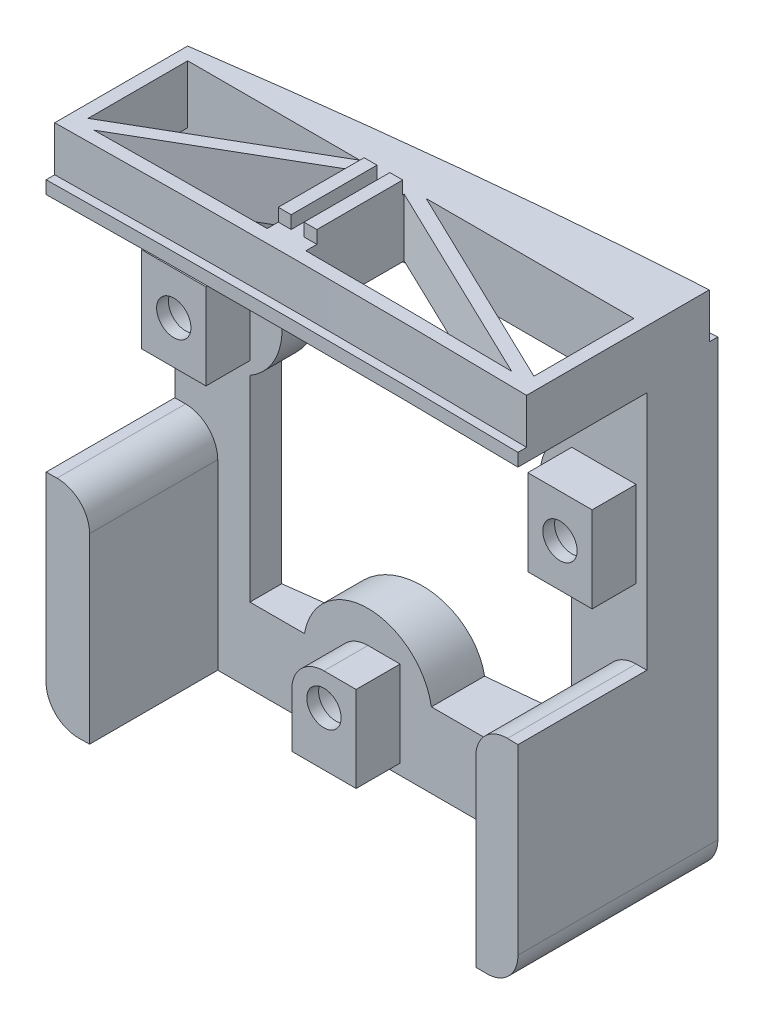
SolidWorks part; units mm, degrees
ref_plane "Front Plane" through (0, 0, 0) normal (0, 0, 1) x (1, 0, 0)
ref_plane "Top Plane" through (0, 0, 0) normal (0, 1, 0) x (1, 0, 0)
ref_plane "Right Plane" through (0, 0, 0) normal (1, 0, 0) x (0, 0, -1)
sketch "Sketch1" plane through (0, 0, 0) normal (0, 1, 0) x (1, 0, 0)
  line L0 (-144.1303, -12.9929) -> (155.8697, -12.8308) construction
  line L1 (-29.3738, 9.8314) -> (-29.3738, -4.1686)
  line L2 (14.6262, 14.4548) -> (14.6262, -4.183)
  line L5 (-29.3738, -2.9686) -> (14.6262, -2.9686)
  line L12 (-51.1303, 9.4041) -> (-59.1513, -7.7971) construction
  line L13 (-109.8536, -6.9996) -> (-109.986, -6.1605)
  line L14 (-10.9303, 7.0314) -> (-9.7303, 7.0314)
  line L15 (-10.9303, 7.0314) -> (-10.9303, -0.9686)
  line L16 (-10.9303, -0.9686) -> (-9.7303, -0.9686)
  line L17 (-9.7303, 7.0314) -> (-9.7303, -0.9686)
  line L18 (-8.5303, 7.0314) -> (-7.3303, 7.0314)
  line L19 (-8.5303, 7.0314) -> (-8.5303, -0.9686)
  line L20 (-8.5303, -0.9686) -> (-7.3303, -0.9686)
  line L21 (-7.3303, 7.0314) -> (-7.3303, -0.9686)
  circle A2 centre (-36.6303, 2.3202) radius 4.25
  arc A9 (-58.7697, -6.9788) -> (-58.7632, -6.9861) centre (-51.1303, -0.0856) ccw
  ellipse E0 centre (-36.6303, 2.3202) end of major axis (-36.1292, -4.0323) minor radius 5.05
  spline S0 degree 13 poles (-110.7235, -3.2524) (-98.8326, -0.2567) (-86.3944, 2.6358) (-73.4943, 5.427) (-60.2589, 8.0815) (-46.8275, 10.5453) (-33.3355, 12.7584) (-19.9065, 14.665) (-6.6486, 16.2187) (6.3449, 17.3865) (18.9944, 18.15) (31.2324, 18.5052) (43.0009, 18.4619) (54.25, 18.0415) knots 0.038912 0.038912 0.038912 0.038912 0.038912 0.038912 0.038912 0.038912 0.038912 0.038912 0.038912 0.038912 0.038912 0.038912 0.206425 0.206425 0.206425 0.206425 0.206425 0.206425 0.206425 0.206425 0.206425 0.206425 0.206425 0.206425 0.206425 0.206425
  spline S1 degree 3 poles (-105.7874, -5.9402) (-105.4515, -5.8576) (-103.7907, -5.4506) (-99.0842, -4.3142) (-91.5415, -2.5615) (-82.0457, -0.4684) (-69.1527, 2.2208) (-52.7063, 5.3568) (-32.7854, 8.6244) (-12.9944, 11.2716) (3.1558, 12.8711) (15.7533, 13.7541) (25.0163, 14.2135) (32.556, 14.4255) (38.4824, 14.4928) (41.3869, 14.4927) (42.8464, 14.4842) knots 0.043242 0.043242 0.043242 0.043242 0.044325 0.048583 0.058255 0.067926 0.077598 0.096941 0.116284 0.135628 0.154971 0.164642 0.174314 0.183986 0.188821 0.193657 0.193657 0.193657 0.193657
  spline S2 degree 3 poles (42.3412, -4.3021) (39.1703, -4.1474) (32.8439, -3.8739) (20.0493, -3.4589) (3.9637, -3.1861) (-15.3945, -3.1849) (-34.7131, -3.4228) (-53.9413, -3.8315) (-69.8279, -4.2978) (-82.3956, -4.7634) (-91.7251, -5.1693) (-99.1578, -5.5509) (-103.8174, -5.8207) (-105.4427, -5.9191) (-105.7874, -5.9402) knots 0.702444 0.702444 0.702444 0.702444 0.71714 0.731836 0.761227 0.790619 0.820011 0.849403 0.878795 0.89349 0.908186 0.922882 0.929138 0.930826 0.930826 0.930826 0.930826
  spline S3 degree 3 poles (-109.986, -6.1605) (-109.4642, -6.0291) (-108.4175, -5.7667) (-103.5943, -4.5692) (-94.8971, -2.4925) (-82.0108, 0.3758) (-63.7471, 4.1371) (-40.3543, 8.3552) (-16.9896, 11.6162) (1.2883, 13.4985) (14.7075, 14.5233) (27.7627, 15.1448) (36.8021, 15.2972) (42.0404, 15.2892) (43.1567, 15.2825) (43.6671, 15.2784) knots 0.038912 0.038912 0.038912 0.038912 0.040616 0.04232 0.054528 0.06816 0.081792 0.109056 0.13632 0.149952 0.163584 0.177216 0.190848 0.192861 0.194565 0.194565 0.194565 0.194565
  spline S4 degree 13 poles (52.5193, -8.6666) (40.2713, -7.9192) (27.7839, -7.3485) (15.1503, -6.9773) (2.4425, -6.804) (-10.2886, -6.8041) (-23.0116, -6.9375) (-35.7087, -7.1592) (-48.3688, -7.4339) (-60.9767, -7.7494) (-73.5011, -8.1244) (-85.8777, -8.6024) (-97.9897, -9.2254) (-109.6522, -9.993) knots 0.686195 0.686195 0.686195 0.686195 0.686195 0.686195 0.686195 0.686195 0.686195 0.686195 0.686195 0.686195 0.686195 0.686195 0.937578 0.937578 0.937578 0.937578 0.937578 0.937578 0.937578 0.937578 0.937578 0.937578 0.937578 0.937578 0.937578 0.937578
  spline S5 degree 3 poles (-110.5235, -4.0272) (-108.9029, -3.6189) (-105.6763, -2.8183) (-99.0735, -1.2268) (-90.6514, 0.7176) (-80.2925, 2.9758) (-67.9991, 5.4979) (-58.7506, 7.2436) (-50.652, 8.6798) (-47.6807, 9.1904) (-44.5606, 9.7093) (-38.2765, 10.745) (-25.0157, 12.7601) (-5.2278, 15.1631) (12.1229, 16.5847) (25.5727, 17.2429) (35.4177, 17.4948) (43.3901, 17.504) (49.633, 17.3925) (52.6803, 17.2987) (54.2127, 17.2415) knots 0.038912 0.038912 0.038912 0.038912 0.044146 0.049381 0.059851 0.07032 0.08079 0.096446 0.097403 0.1044 0.105092 0.106475 0.122668 0.143607 0.164546 0.175016 0.185486 0.195955 0.20119 0.206425 0.206425 0.206425 0.206425
  spline S6 degree 3 poles (52.5681, -7.868) (50.9024, -7.7664) (47.578, -7.5733) (40.8667, -7.2231) (32.4163, -6.8574) (22.195, -6.5335) (8.4979, -6.2488) (-8.6998, -6.1472) (-26.1679, -6.3047) (-37.8303, -6.5029) (-44.675, -6.6412) (-49.0049, -6.7375) (-53.5282, -6.8475) (-56.9797, -6.937) (-62.6027, -7.0912) (-70.3002, -7.3251) (-80.3346, -7.6831) (-90.3076, -8.1048) (-98.4897, -8.5174) (-104.9445, -8.8903) (-108.1134, -9.09) (-109.7048, -9.1947) knots 0.686195 0.686195 0.686195 0.686195 0.69405 0.701906 0.717617 0.733329 0.74904 0.780463 0.811886 0.82883 0.833892 0.843309 0.848739 0.854731 0.859237 0.874732 0.890444 0.906155 0.921867 0.929722 0.937578 0.937578 0.937578 0.937578
  spline S7 degree 3 poles (43.1189, -5.1414) (42.5664, -5.1139) (40.3515, -5.0059) (33.6908, -4.7068) (23.0612, -4.3421) (5.0464, -3.9837) (-17.5716, -3.9643) (-44.6283, -4.3923) (-66.9803, -4.9899) (-84.5965, -5.6437) (-96.3916, -6.1935) (-104.7586, -6.6717) (-108.8142, -6.9312) (-109.8536, -6.9996) knots 0.701175 0.701175 0.701175 0.701175 0.703751 0.711493 0.7321 0.752708 0.793923 0.835139 0.876354 0.896962 0.917569 0.932426 0.937578 0.937578 0.937578 0.937578
  spline S8 degree 3 poles (43.0791, -5.9404) (39.8994, -5.7822) (33.5559, -5.5021) (20.7207, -5.0752) (4.577, -4.7906) (-14.8622, -4.781) (-29.9542, -4.963) (-38.7515, -5.1226) (-41.4966, -5.1769) (-43.935, -5.226) (-46.8305, -5.2883) (-49.9812, -5.3611) (-51.9548, -5.4083) (-59.5635, -5.5969) (-69.6735, -5.894) (-82.18, -6.356) (-91.5501, -6.7627) (-99.2415, -7.157) (-105.3139, -7.5106) (-108.2984, -7.6991) (-109.7967, -7.7977) knots 0.701175 0.701175 0.701175 0.701175 0.71595 0.730726 0.760276 0.789826 0.819377 0.829214 0.830132 0.831967 0.840401 0.843428 0.846456 0.849484 0.878477 0.893252 0.908028 0.922803 0.93019 0.937578 0.937578 0.937578 0.937578
  spline S9 degree 3 poles (-110.1814, -5.3848) (-108.6794, -5.0063) (-105.6878, -4.2632) (-99.5742, -2.785) (-91.7846, -0.9758) (-82.2124, 1.1324) (-69.613, 3.7573) (-59.5108, 5.6872) (-50.135, 7.3499) (-46.7114, 7.9355) (-40.1955, 9.0106) (-29.5503, 10.6773) (-12.6029, 12.9298) (3.6765, 14.5228) (16.3735, 15.3941) (25.7087, 15.8415) (33.3064, 16.0409) (39.2778, 16.0967) (42.204, 16.0903) (43.6745, 16.0785) knots 0.038912 0.038912 0.038912 0.038912 0.043776 0.04864 0.058368 0.068097 0.077825 0.096092 0.09776 0.105207 0.106069 0.116738 0.136195 0.155652 0.16538 0.175108 0.184837 0.189701 0.194565 0.194565 0.194565 0.194565
  dimension "D1" = 8.5
  dimension "D2" = 14
  dimension "D3" = 44
  dimension "D4" = 1.2
  dimension "D5" = 26.9
  dimension "D6" = 28.1
  dimension "D7" = 8
  dimension "D8" = 8
  dimension "D9" = 2
  dimension "D10" = 2
  dimension "D11" = 1.2
  dimension "D12" = 1.2
extrude "Boss-Extrude2" add sketch "Sketch1" against normal blind 47.8 contours S3 L1 S1 L2 | S1 L1 L5 L2 | S2 L2 L5 L1 | S7 L2 S2 L1 | L17 L14 L15 L16 | L21 L18 L19 L20 region at (-7.4038, 0, -12.035) region at (-6.1165, 0, -4.438) region at (-7.397, 0, 3.1176) region at (-7.3732, 0, 3.6567) region at (-10.3303, 0, -3.0314) region at (-7.9303, 0, -3.0314)
extrude "Cut-Extrude1" cut sketch "Sketch1<3>" against normal blind 4.2 contours S7 L2 S2 L1 | S3 L1 S1 L2 region at (-7.4038, 0, -12.035) region at (-7.3732, 0, 3.6567)
sketch "Sketch1<3>" plane through (0, 0, 0) normal (0, 1, 0) x (1, 0, 0) same geometry as "Sketch1"
sketch "Sketch2" plane through (0, 0, 0) normal (0, 1, 0) x (1, 0, 0)
  line L0 (-29.3738, 7.8314) -> (14.6262, 7.8314)
  line L1 (-29.3738, 9.8314) -> (-29.3738, -4.1686) construction
  line L2 (14.6262, 14.4548) -> (14.6262, -4.183) construction
  line L3 (-29.3738, -2.9686) -> (14.6262, -2.9686) construction
  line L4 (-29.3738, -2.9686) -> (14.6262, -2.9686)
  line L5 (14.6262, 14.4548) -> (14.6262, -4.183)
  line L6 (-29.3738, 9.8314) -> (-29.3738, -4.1686)
  spline S0 degree 3 poles (-1947.4588, -167.681) (424.4026, -117.2665) (271.9813, -15.4064) (33.6908, -4.7068) (23.0612, -4.3421) (5.0464, -3.9837) (-17.5716, -3.9643) (-44.6283, -4.3923) (-66.9803, -4.9899) (-84.5965, -5.6437) (-96.3916, -6.1935) (-281.2066, -16.7558) (-334.7502, -73.0291) (1880.8527, -187.1354) knots -0.374252 -0.374252 -0.374252 -0.374252 0.703751 0.711493 0.7321 0.752708 0.793923 0.835139 0.876354 0.896962 0.917569 0.932426 1.794118 1.794118 1.794118 1.794118 only from (43.1189, -5.1414) to (-109.8536, -6.9996) construction
  spline S1 degree 3 poles (43.1189, -5.1414) (42.5664, -5.1139) (40.3515, -5.0059) (33.6908, -4.7068) (23.0612, -4.3421) (5.0464, -3.9837) (-17.5716, -3.9643) (-44.6283, -4.3923) (-66.9803, -4.9899) (-84.5965, -5.6437) (-96.3916, -6.1935) (-104.7586, -6.6717) (-108.8142, -6.9312) (-109.8536, -6.9996) knots 0.701175 0.701175 0.701175 0.701175 0.703751 0.711493 0.7321 0.752708 0.793923 0.835139 0.876354 0.896962 0.917569 0.932426 0.937578 0.937578 0.937578 0.937578
  spline M3 degree 3 poles (-105.7874, -5.9402) (-105.4427, -5.9191) (-103.8174, -5.8207) (-99.1578, -5.5509) (-91.7251, -5.1693) (-82.3956, -4.7634) (-69.8279, -4.2978) (-53.9413, -3.8315) (-34.7131, -3.4228) (-15.3945, -3.1849) (3.9637, -3.1861) (20.0493, -3.4589) (32.8439, -3.8739) (39.1703, -4.1474) (42.3412, -4.3021) knots 0.702444 0.702444 0.702444 0.702444 0.704132 0.710388 0.725084 0.739779 0.754475 0.783867 0.813259 0.842651 0.872042 0.901434 0.91613 0.930826 0.930826 0.930826 0.930826 only from (-29.3738, -3.3687) to (14.6262, -3.383)
  line M4 (14.6262, -3.383) -> (14.6262, 13.6533)
  line M6 (-29.3738, 9.0233) -> (-29.3738, -3.3687)
  dimension "D1" = 2
extrude "Cut-Extrude2" cut sketch "Sketch2" against normal through all from offset 5.4 contours L4 L0 M6 M4 | L4 M6 M3 M4 | S1 L5 L6 M3 region at (-7.3738, 0, -2.4314) region at (-7.3795, 0, 3.5139) offset against normal yes
sketch "Sketch3" plane through (0, 0, -7.8314) normal (0, 0, 1) x (1, 0, 0)
  line L0 (14.6262, -47.8) -> (14.6262, -5.4) construction
  line L1 (-29.3738, -47.8) -> (14.6262, -47.8) construction
  circle A0 centre (-11.3738, -41.8) radius 2.5
  circle A1 centre (-25.3738, -17.3) radius 2.5
  circle A2 centre (10.6262, -17.3) radius 2.5
  dimension "D1" = 5
  dimension "D2" = 14
  dimension "D3" = 36
  dimension "D4" = 4
  dimension "D5" = 24.5
  dimension "D6" = 6
extrude "Cut-Extrude3" cut sketch "Sketch3" against normal through all
sketch "Sketch4" plane through (0, 0, -7.8314) normal (0, 0, 1) x (1, 0, 0)
  line L0 (-28.3738, -13.3) -> (-22.3738, -13.3)
  line L1 (-28.3738, -13.3) -> (-28.3738, -21.3)
  line L2 (-28.3738, -21.3) -> (-22.3738, -21.3)
  line L3 (-22.3738, -13.3) -> (-22.3738, -21.3)
  line L4 (7.6262, -13.3) -> (13.6262, -13.3)
  line L5 (7.6262, -13.3) -> (7.6262, -21.3)
  line L6 (7.6262, -21.3) -> (13.6262, -21.3)
  line L7 (13.6262, -13.3) -> (13.6262, -21.3)
  line L9 (-14.3738, -41.8) -> (-14.3738, -46.8)
  line L10 (-14.3738, -46.8) -> (-8.3738, -46.8)
  line L11 (-8.3738, -38.8) -> (-8.3738, -46.8)
  line L12 (-29.3738, -47.8) -> (-29.3738, -5.4) construction
  line L13 (14.6262, -47.8) -> (14.6262, -5.4) construction
  line L14 (-29.3738, -47.8) -> (14.6262, -47.8) construction
  line L15 (-11.3738, -38.8) -> (-8.3738, -38.8)
  arc A0 (-11.3738, -38.8) -> (-14.3738, -41.8) centre (-11.3738, -41.8) ccw
  point P23 (-25.3738, -21.3)
  dimension "D11" = 28.5
  dimension "D12" = 3
  dimension "D1" = 1
  dimension "D2" = 8
  dimension "D3" = 6
  dimension "D4" = 6
  dimension "D5" = 8
  dimension "D6" = 1
  dimension "D7" = 1
  dimension "D8" = 8
  dimension "D9" = 6
  dimension "D10" = 14
extrude "Boss-Extrude4" add sketch "Sketch4" along normal blind 4.1
sketch "Sketch8" plane through (0, 0, -7.8314) normal (0, 0, 1) x (1, 0, 0)
  circle A0 centre (10.6262, -17.3) radius 1.6
  circle A1 centre (-25.3738, -17.3) radius 1.6
  circle A2 centre (-11.3738, -41.8) radius 1.6
  dimension "D1" = 3.2
extrude "Cut-Extrude6" cut sketch "Sketch8" against normal through all both and the other way through all
ref_plane "Plane3" through (0, 0, -4.8314) normal (0, 0, 1) x (1, 0, 0)
ref_plane "Plane1" through (0, 0, -8.0314) normal (0, 0, 1) x (1, 0, 0)
sketch "Sketch9" plane through (0, 0, -8.0314) normal (0, 0, 1) x (1, 0, 0)
  circle A0 centre (10.6262, -17.3) radius 2.5
  circle A1 centre (-25.3738, -17.3) radius 2.5
  circle A2 centre (-11.3738, -41.8) radius 2.5
  dimension "D1" = 5
ref_plane "Plane2" through (0, 0, -9.0314) normal (0, 0, 1) x (1, 0, 0)
sketch "Sketch10" plane through (0, 0, -9.0314) normal (0, 0, 1) x (1, 0, 0)
  circle A0 centre (10.6262, -17.3) radius 2.7
  circle A1 centre (-11.3738, -41.8) radius 2.7
  circle A2 centre (-25.3738, -17.3) radius 2.7
  dimension "D1" = 5.4
loft "Cut-Loft2" cut section "Sketch9" section "Sketch10" connector at (9.6622, -19.6067, -8.0314) connector at (10.8262, -19.9926, -9.0314)
loft "Cut-Loft3" cut section "Sketch10<8>" section "Sketch9<8>" connector at (-23.8675, -15.0593, -9.0314) connector at (-23.8366, -15.3285, -8.0314)
sketch "Sketch10<8>" plane through (0, 0, -9.0314) normal (0, 0, 1) x (1, 0, 0) same geometry as "Sketch10"
sketch "Sketch9<8>" plane through (0, 0, -8.0314) normal (0, 0, 1) x (1, 0, 0) same geometry as "Sketch9"
loft "Cut-Loft4" cut section "Sketch10<9>" section "Sketch9<9>" connector at (-9.5256, -39.8318, -9.0314) connector at (-9.7018, -39.9414, -8.0314)
sketch "Sketch10<9>" plane through (0, 0, -9.0314) normal (0, 0, 1) x (1, 0, 0) same geometry as "Sketch10"
sketch "Sketch9<9>" plane through (0, 0, -8.0314) normal (0, 0, 1) x (1, 0, 0) same geometry as "Sketch9"
sketch "Sketch12" plane through (0, 0, -4.8314) normal (0, 0, 1) x (1, 0, 0)
  circle A1 centre (-25.3738, -17.3) radius 2.5
  circle A2 centre (10.6262, -17.3) radius 2.5
  circle A3 centre (-11.3738, -41.8) radius 2.5
  dimension "D1" = 5
extrude "Cut-Extrude10" cut sketch "Sketch12" against normal through all
sketch "Sketch13" plane through (0, 0, -7.8314) normal (0, 0, 1) x (1, 0, 0)
  circle A0 centre (-25.3738, -17.3) radius 3
  circle A1 centre (10.6262, -17.3) radius 3
  circle A2 centre (-11.3738, -41.8) radius 3
  dimension "D1" = 6
extrude "Cut-Extrude11" cut sketch "Sketch13" against normal through all from surface starting at plane "Plane2"
sketch "Sketch14" plane through (0, 0, -7.8314) normal (0, 0, 1) x (1, 0, 0)
  line L0 (-22.3738, -21.3) -> (-22.3738, -13.3) construction
  line L1 (-22.3738, -6.2) -> (7.6262, -6.2)
  line L2 (-22.3738, -6.2) -> (-22.3738, -40.8)
  line L3 (-22.3738, -40.8) -> (7.6262, -40.8)
  line L4 (7.6262, -6.2) -> (7.6262, -40.8)
  line L6 (7.6262, -13.3) -> (7.6262, -21.3) construction
  line L7 (-29.3738, -5.4) -> (14.6262, -5.4) construction
  line L8 (-29.3738, -47.8) -> (14.6262, -47.8) construction
  circle A0 centre (-11.3738, -41.8) radius 6
  circle A1 centre (-25.3738, -17.3) radius 6
  circle A2 centre (10.6262, -17.3) radius 6
  dimension "D3" = 12
  dimension "D1" = 0.8
  dimension "D2" = 7
extrude "Cut-Extrude15" cut sketch "Sketch14" against normal through all contours A2 L4 L1 L2 A1 L3 A0 region at (-7.1859, -23.0743, -7.8314)
extrude "Boss-Extrude5" add sketch "Sketch1<4>" along normal blind 1.2 contours L17 L14 L15 L16 | L21 L18 L19 L20 region at (-10.3303, 0, -3.0314) region at (-7.9303, 0, -3.0314)
sketch "Sketch1<4>" plane through (0, 0, 0) normal (0, 1, 0) x (1, 0, 0) same geometry as "Sketch1"
sketch "Sketch16" plane through (0, 0, 0) normal (0, 1, 0) x (1, 0, 0)
  line L0 (-29.3738, 7.8314) -> (14.6262, 7.8314) construction
  line L1 (-29.3738, 7.8314) -> (14.6262, 7.8314)
  line L2 (-28.1738, 7.8314) -> (-28.1738, -3.3521)
  line L3 (13.4262, 7.8314) -> (13.4262, -3.3616)
  line L4 (-29.3738, 9.0233) -> (-29.3738, -3.3687) construction
  line L5 (14.6262, 13.6533) -> (14.6262, -3.383) construction
  line L6 (-10.9303, 7.8314) -> (-10.9303, -2.004)
  line L7 (-7.3303, 7.8314) -> (-7.3303, -1.9972)
  line L8 (-10.9303, 7.0314) -> (-10.9303, -0.9686) construction
  line L9 (-7.3303, 7.0314) -> (-7.3303, -0.9686) construction
  line L10 (-10.9303, 7.8314) -> (-28.1738, -2.152) construction
  line L11 (-7.3303, 7.8314) -> (13.4262, -2.1614) construction
  line L12 (-11.2309, 8.3507) -> (-28.4745, -1.6327)
  line L13 (-10.6297, 7.3122) -> (-27.8732, -2.6712)
  line L14 (-7.5906, 7.2908) -> (13.1659, -2.702)
  line L15 (-7.07, 8.3721) -> (13.6864, -1.6208)
  circle A0 centre (-10.9303, 7.8314) radius 0.6
  circle A1 centre (-7.3303, 7.8314) radius 0.6
  circle A2 centre (13.4262, -2.1614) radius 0.6
  circle A3 centre (-28.1738, -2.152) radius 0.6
  spline S0 degree 3 poles (-911.8741, -1709.024) (611.2322, -138.1951) (312.6294, -3.2064) (-384.575, -3.1606) (-743.4746, -142.8958) (590.663, 1832.5542) knots -0.674113 -0.674113 -0.674113 -0.674113 0.761227 0.790619 2.5016 2.5016 2.5016 2.5016 only from (14.6262, -3.383) to (-29.3738, -3.3687) construction
  spline S1 degree 3 poles (14.6262, -3.383) (11.0735, -3.3176) (1.077, -3.186) (-13.6131, -3.185) (-24.7175, -3.3027) (-29.3738, -3.3687) knots 0.744984 0.744984 0.744984 0.744984 0.761227 0.790619 0.811897 0.811897 0.811897 0.811897
  spline S2 degree 1 poles (14.6482, -2.1832) (-29.3908, -2.1688) knots 0 0 1 1 construction
  spline S3 degree 3 poles (14.6482, -2.1832) (14.3424, -2.1776) (13.8336, -2.1684) (10.1691, -2.1054) (3.4513, -2.0227) (-3.6711, -1.995) (-7.9303, -1.9975) (-9.1304, -1.9994) (-10.3303, -2.002) (-13.4178, -2.0117) (-19.3679, -2.0473) (-24.9153, -2.1078) (-28.5796, -2.1575) (-29.0863, -2.1645) (-29.3908, -2.1688) knots 0.744984 0.744984 0.744984 0.744984 0.746379 0.747309 0.761712 0.777009 0.779741 0.781107 0.782474 0.785206 0.795169 0.809581 0.810507 0.811897 0.811897 0.811897 0.811897
  line M7 (-7.3303, 7.0314) -> (-7.3303, -0.9686)
  line M18 (-10.9303, -0.9686) -> (-10.9303, 7.0314)
  dimension "D4" = 1.2
  dimension "D1" = 1.2
  dimension "D2" = 1.2
  dimension "D3" = 1.2
  dimension "D5" = 0.6
  dimension "D6" = 0.6
  dimension "D7" = 0.6
  dimension "D8" = 0.6
extrude "Cut-Extrude16" cut sketch "Sketch16" against normal up to surface (5.4 mm away) contours L12 L1 L2 | S3 L6 L13 M18 | S3 L14 L7 M7 | L1 L15 L3 region at (-22.8251, 0, -4.7347) region at (-16.2622, 0, -1.0082) region at (6.9684, 0, -4.7225) region at (-0.908, 0, -1.0279) up to face at (-1.8738, -5.4, -3.326)
sketch "Sketch17" plane through (0, -5.4, 0) normal (0, -1, 0) x (1, 0, 0)
  line L1 (-29.3738, -7.8314) -> (-25.3738, -7.8314)
  line L2 (-29.3738, -7.8314) -> (-29.3738, 4.1686)
  line L4 (-25.3738, -7.8314) -> (-25.3738, 4.116)
  line L5 (14.6262, -7.8314) -> (10.6262, -7.8314)
  line L6 (14.6262, -7.8314) -> (14.6262, 4.183)
  line L8 (10.6262, -7.8314) -> (10.6262, 4.1171)
  spline S1 degree 3 poles (-2306.1321, 1827.3013) (638.0841, 168.2186) (333.7885, 4.2655) (-443.3135, 3.5992) (-853.1067, 184.262) (1543.1181, -2468.2322) knots -0.765514 -0.765514 -0.765514 -0.765514 0.752708 0.793923 2.774645 2.774645 2.774645 2.774645 only from (14.6262, 4.183) to (-29.3738, 4.1686) construction
  spline S2 degree 3 poles (14.6262, 4.183) (12.9332, 4.1518) (2.2231, 3.9812) (-12.4727, 3.9686) (-25.4391, 4.1127) (-29.3738, 4.1686) knots 0.744962 0.744962 0.744962 0.744962 0.752708 0.793923 0.81191 0.81191 0.81191 0.81191
  point P10 (0, 0)
  point P14 (0, 0)
  point P15 (0, 0)
  line M5 (11.9939, 2.1378) -> (-7.3303, -7.1655)
  spline M7 degree 3 poles (14.6482, 2.1832) (14.3424, 2.1776) (13.8336, 2.1684) (10.1691, 2.1054) (3.4513, 2.0227) (-3.6711, 1.995) (-7.9303, 1.9975) (-9.1304, 1.9994) (-10.3303, 2.002) (-13.4178, 2.0117) (-19.3679, 2.0473) (-24.9153, 2.1078) (-28.5796, 2.1575) (-29.0863, 2.1645) (-29.3908, 2.1688) knots 0.744984 0.744984 0.744984 0.744984 0.746379 0.747309 0.761712 0.777009 0.779741 0.781107 0.782474 0.785206 0.795169 0.809581 0.810507 0.811897 0.811897 0.811897 0.811897 only from (-7.3303, 1.9972) to (11.9939, 2.1378)
  line M8 (13.4262, 1.4955) -> (13.4262, -7.8314)
  line M9 (13.4262, -7.8314) -> (14.6262, -7.8314)
  line M10 (14.6262, -7.8314) -> (14.6262, 4.183)
  spline M11 degree 3 poles (43.1189, 5.1414) (42.5664, 5.1139) (40.3515, 5.0059) (33.6908, 4.7068) (23.0612, 4.3421) (5.0464, 3.9837) (-17.5716, 3.9643) (-44.6283, 4.3923) (-66.9803, 4.9899) (-84.5965, 5.6437) (-96.3916, 6.1935) (-104.7586, 6.6717) (-108.8142, 6.9312) (-109.8536, 6.9996) knots 0.701175 0.701175 0.701175 0.701175 0.703751 0.711493 0.7321 0.752708 0.793923 0.835139 0.876354 0.896962 0.917569 0.932426 0.937578 0.937578 0.937578 0.937578 only from (14.6262, 4.183) to (-29.3738, 4.1686)
  line M12 (-29.3738, 4.1686) -> (-29.3738, -7.8314)
  line M13 (-29.3738, -7.8314) -> (-28.1738, -7.8314)
  line M14 (-28.1738, -7.8314) -> (-28.1738, 1.4587)
  line M15 (-28.1738, 1.4587) -> (-12.1278, -7.8314)
  line M17 (-5.9471, -7.8314) -> (13.4262, 1.4955)
  line M19 (-10.9303, -7.1381) -> (-26.9484, 2.1358)
  spline M20 degree 3 poles (14.6482, 2.1832) (14.3424, 2.1776) (13.8336, 2.1684) (10.1691, 2.1054) (3.4513, 2.0227) (-3.6711, 1.995) (-7.9303, 1.9975) (-9.1304, 1.9994) (-10.3303, 2.002) (-13.4178, 2.0117) (-19.3679, 2.0473) (-24.9153, 2.1078) (-28.5796, 2.1575) (-29.0863, 2.1645) (-29.3908, 2.1688) knots 0.744984 0.744984 0.744984 0.744984 0.746379 0.747309 0.761712 0.777009 0.779741 0.781107 0.782474 0.785206 0.795169 0.809581 0.810507 0.811897 0.811897 0.811897 0.811897 only from (-26.9484, 2.1358) to (-10.9303, 2.004)
  dimension "D1" = 4
  dimension "D2" = 4
extrude "Boss-Extrude6" add sketch "Sketch17" against normal blind 20 from surface contours L1 L4 M15 M14 | L8 L5 M8 M17 | L4 M15 M19 M20 M11 M12 M13 M14 | L8 M17 M8 M9 M10 M11 M7 M5 | L8 M5 M7 | L4 M19 M20 region at (-29.2473, -5.4, -1.8314) region at (12.6283, -5.4, 4.0215) region at (-26.8184, -5.4, -3.5787) region at (12.0625, -5.4, -3.4962) starting at face at (-12.8738, -47.8, -10.4873)
fillet "Fillet1" radius 3 4 edges at (10.6262, -27.8, -1.8572) (-25.3738, -27.8, -1.8577)
